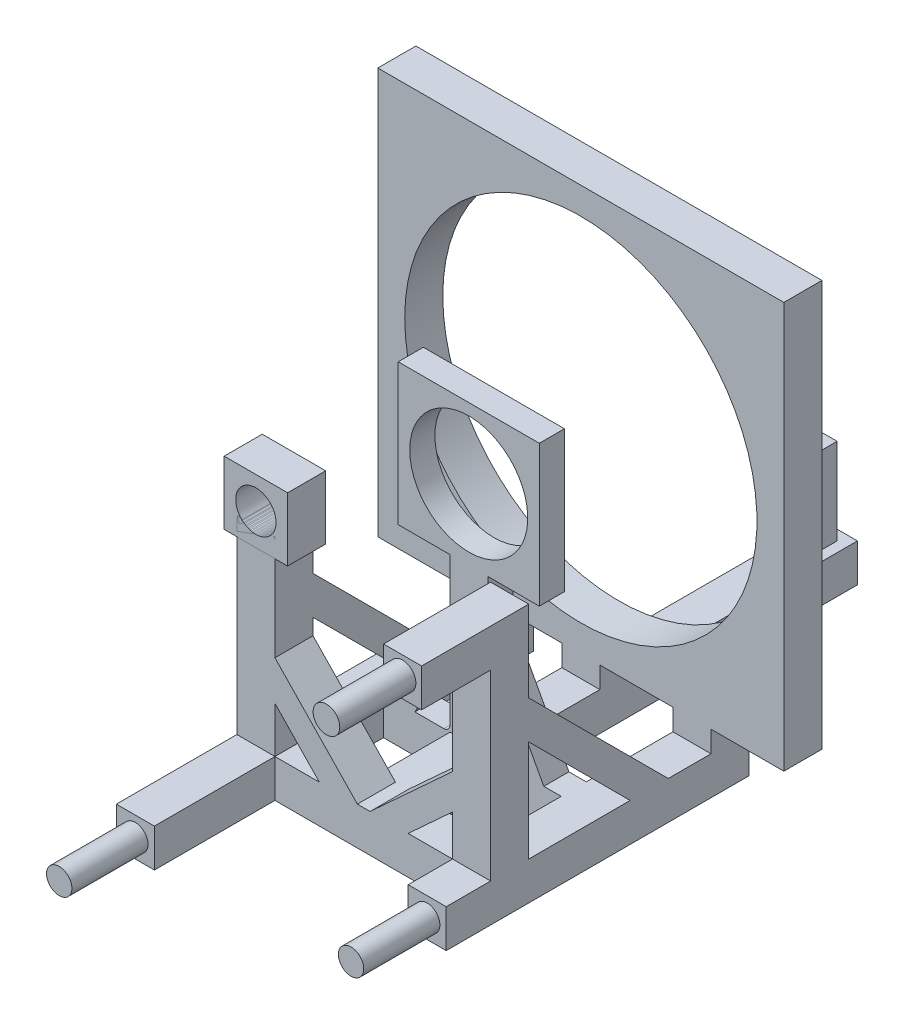
SolidWorks part; units mm, degrees
other "Markup1"
sketch "Sketch15" plane through (18.05, 14, 0) normal (0.0458, 0.1049, 0.9934) x (0.9989, -0.0157, -0.0444)
other "Markup2"
sketch "Sketch46" plane through (24.24, 35.18, 6) normal (0.2146, 0.4944, 0.8423) x (0.973, -0.1833, -0.1403)
ref_plane "Front Plane" through (0, 0, 0) normal (0, 0, 1) x (1, 0, 0)
ref_plane "Top Plane" through (0, 0, 0) normal (0, 1, 0) x (1, 0, 0)
ref_plane "Right Plane" through (0, 0, 0) normal (1, 0, 0) x (0, 0, -1)
sketch "Sketch3" plane through (0, 0, 0) normal (0, 0, 1) x (1, 0, 0)
  line L1 (-1.5, 1.5) -> (1.5, 1.5)
  line L2 (-1.5, 1.5) -> (-1.5, -1.5)
  line L3 (-1.5, -1.5) -> (1.5, -1.5)
  line L4 (1.5, 1.5) -> (1.5, -1.5)
  line L5 (-1.5, 1.5) -> (1.5, -1.5) construction
  line L6 (-1.5, -1.5) -> (1.5, 1.5) construction
  point P0 (0, 0)
  dimension "D1" = 3
  dimension "D3" = 0
  dimension "D2" = 3
  dimension "D4" = 0
sketch "Sketch4" plane through (0, 0, 0) normal (0, 1, 0) x (1, 0, 0)
  line L0 (0, 0) -> (0, 11)
  line L1 (0, 11) -> (17, 11)
  line L2 (17, 11) -> (17, 6)
  dimension "D1" = 17
  dimension "D2" = 11
  dimension "D3" = 5
sweep "Sweep3" add profiles "Sketch3" path "Sketch4"
sketch "Sketch7" plane through (0, 0, 0) normal (0, 1, 0) x (1, 0, 0)
  line L2 (-1.5, 12.5) -> (1.5, 12.5)
  line L3 (-1.5, 12.5) -> (-1.5, 9.5)
  line L4 (-1.5, 9.5) -> (1.5, 9.5)
  line L5 (1.5, 12.5) -> (1.5, 9.5)
  line L6 (-1.5, 12.5) -> (1.5, 9.5) construction
  line L7 (-1.5, 9.5) -> (1.5, 12.5) construction
  point P0 (0, 11)
  dimension "D1" = 1.5
  dimension "D2" = 3
extrude "Boss-Extrude1" add sketch "Sketch7" along normal blind 16.5
ref_plane "Plane8" through (0, 0, -11) normal (0, 0, 1) x (1, 0, 0)
sketch "Sketch12" plane through (0, 0, -11) normal (0, 0, 1) x (1, 0, 0)
  line L1 (-2.5, 20) -> (2.5, 20)
  line L2 (-2.5, 20) -> (-2.5, 15)
  line L3 (-2.5, 15) -> (2.5, 15)
  line L4 (2.5, 20) -> (2.5, 15)
  line L5 (-2.5, 20) -> (2.5, 15) construction
  line L6 (-2.5, 15) -> (2.5, 20) construction
  point P0 (0, 17.5)
  dimension "D1" = 17.5
  dimension "D2" = 5
  dimension "D3" = 1.5
  dimension "D4" = 5
extrude "Boss-Extrude4" add sketch "Sketch12" along normal mid plane 3 separate body
ref_plane "Plane9" through (9.09, 0, 0) normal (1, 0, 0) x (0, 0, -1)
sketch "Sketch16" plane through (0, 0, -12.5) normal (0, 0, -1) x (-1, 0, 0)
  circle A0 centre (0, 17.5) radius 1.59
sketch "Sketch17" plane through (0, 0, 0) normal (0, 0, 1) x (1, 0, 0)
  circle A0 centre (0, 0) radius 1
  dimension "D1" = 2
extrude "Boss-Extrude5" add sketch "Sketch17" along normal blind 6
sketch "Sketch18" plane through (0, 0, -6) normal (0, 0, 1) x (1, 0, 0)
  line L0 (18.5, 1.5) -> (18.5, -1.5) construction
  line L1 (15.5, 1.5) -> (18.5, 1.5) construction
  circle A0 centre (17, 0) radius 1
  dimension "D1" = 2
  dimension "D2" = 1.5
  dimension "D3" = 1.5
extrude "Boss-Extrude6" add sketch "Sketch18" along normal blind 6
ref_plane "Plane10" through (0, 0, -12.5) normal (0, 0, 1) x (1, 0, 0)
sketch "Sketch19" plane through (0, 0, -12.5) normal (0, 0, 1) x (1, 0, 0)
  line L0 (1.5, -1.5) -> (15.5, -1.5) construction
  line L1 (6.74, 1.5) -> (9.74, 1.5)
  line L2 (6.74, 1.5) -> (6.74, -1.5)
  line L3 (6.74, -1.5) -> (9.74, -1.5)
  line L4 (9.74, 1.5) -> (9.74, -1.5)
  line L5 (6.74, 1.5) -> (9.74, -1.5) construction
  line L6 (6.74, -1.5) -> (9.74, 1.5) construction
  point P0 (8.24, 0)
  dimension "D1" = 3
  dimension "D2" = 3
  dimension "D3" = 8.24
extrude "Boss-Extrude7" add sketch "Sketch19" against normal blind 7.54 separate body
sketch "Sketch21" plane through (0, 1.5, 0) normal (0, 1, 0) x (1, 0, 0)
  line L0 (9.74, 20.04) -> (9.74, 12.5) construction
  line L1 (6.74, 20.04) -> (9.74, 20.04)
  line L2 (6.74, 20.04) -> (6.74, 18.06)
  line L3 (6.74, 18.06) -> (9.74, 18.06)
  line L4 (9.74, 20.04) -> (9.74, 18.06)
  dimension "D2" = 1.98
extrude "Boss-Extrude8" add sketch "Sketch21" along normal blind 17.68
ref_plane "Plane11" through (0, 0, -19.05) normal (0, 0, 1) x (1, 0, 0)
sketch "Sketch22" plane through (0, 0, -19.05) normal (0, 0, 1) x (1, 0, 0)
  line L2 (2.6571, 24.74) -> (13.7771, 24.74)
  line L3 (2.6571, 24.74) -> (2.6571, 13.62)
  line L4 (2.6571, 13.62) -> (13.7771, 13.62)
  line L5 (13.7771, 24.74) -> (13.7771, 13.62)
  line L6 (2.6571, 24.74) -> (13.7771, 13.62) construction
  line L7 (2.6571, 13.62) -> (13.7771, 24.74) construction
  dimension "D3" = 11.12
  dimension "D4" = 11.12
extrude "Boss-Extrude9" add sketch "Sketch22" along normal mid plane 1.98
sketch "Sketch23" plane through (0, 0, -20.04) normal (0, 0, -1) x (-1, 0, 0)
  circle A0 centre (-8.2171, 19.18) radius 4.65
extrude "Cut-Extrude2" cut sketch "Sketch23" against normal mid plane 5
sketch "Sketch24" plane through (0, 0, -20.04) normal (0, 0, -1) x (-1, 0, 0)
  line L0 (-6.74, 1.5) -> (-9.74, 1.5) construction
  line L1 (-9.74, -1.5) -> (-6.74, -1.5)
  line L2 (-9.74, -1.5) -> (-9.74, 1.5)
  line L3 (-9.74, 1.5) -> (-6.74, 1.5)
  line L4 (-6.74, -1.5) -> (-6.74, 1.5)
  line L5 (-6.74, 1.5) -> (-9.74, 1.5) construction
extrude "Boss-Extrude10" add sketch "Sketch24" along normal blind 9.83
sketch "Sketch25" plane through (0, 1.5, 0) normal (0, 1, 0) x (1, 0, 0)
  line L0 (9.74, 29.87) -> (9.74, 20.04) construction
  line L1 (6.74, 29.87) -> (9.74, 29.87)
  line L2 (6.74, 29.87) -> (6.74, 26.87)
  line L3 (6.74, 26.87) -> (9.74, 26.87)
  line L4 (9.74, 29.87) -> (9.74, 26.87)
  dimension "D1" = 3
extrude "Boss-Extrude11" add sketch "Sketch25" along normal blind 3
ref_plane "Plane12" through (0, 0, -28.37) normal (0, 0, -1) x (-1, 0, 0)
sketch "Sketch27" plane through (0, 0, -28.37) normal (0, 0, -1) x (-1, 0, 0)
  line L2 (-24.24, 35.18) -> (7.76, 35.18)
  line L3 (-24.24, 35.18) -> (-24.24, 3.18)
  line L4 (-24.24, 3.18) -> (7.76, 3.18)
  line L5 (7.76, 35.18) -> (7.76, 3.18)
  line L6 (-24.24, 35.18) -> (7.76, 3.18) construction
  line L7 (-24.24, 3.18) -> (7.76, 35.18) construction
  line L8 (-6.74, 1.5) -> (-9.74, 1.5) construction
  point P0 (-8.24, 19.18)
  dimension "D1" = 17.68
  dimension "D3" = 32
extrude "Boss-Extrude12" add sketch "Sketch27" along normal mid plane 3
sketch "Sketch28" plane through (0, 0, -29.87) normal (0, 0, -1) x (-1, 0, 0)
  circle A0 centre (-8.24, 19.18) radius 13.88
extrude "Cut-Extrude3" cut sketch "Sketch28" against normal blind 7
sketch "Sketch31" plane through (0, 0, -29.87) normal (0, 0, -1) x (-1, 0, 0)
  line L0 (-6.74, 1.5) -> (-9.74, 1.5) construction
  line L1 (-9.74, -1.5) -> (-6.74, -1.5)
  line L2 (-9.74, -1.5) -> (-9.74, 1.5)
  line L3 (-9.74, 1.5) -> (-6.74, 1.5)
  line L4 (-6.74, -1.5) -> (-6.74, 1.5)
  line L5 (-6.74, 1.5) -> (-9.74, 1.5) construction
extrude "Boss-Extrude13" add sketch "Sketch31" along normal blind 17.3
sketch "Sketch32" plane through (0, 1.5, 0) normal (0, 1, 0) x (1, 0, 0)
  line L5 (6.74, 47.17) -> (6.74, 29.87) construction
  line L6 (7.54, 46.37) -> (8.94, 46.37)
  line L7 (7.54, 46.37) -> (7.54, 44.97)
  line L8 (7.54, 44.97) -> (8.94, 44.97)
  line L9 (8.94, 46.37) -> (8.94, 44.97)
  line L10 (7.54, 46.37) -> (8.94, 44.97) construction
  line L11 (7.54, 44.97) -> (8.94, 46.37) construction
  line L12 (6.74, 47.17) -> (9.74, 47.17) construction
  point P0 (8.24, 45.67)
  dimension "D1" = 1.4
  dimension "D2" = 1.4
  dimension "D3" = 1.5
  dimension "D4" = 1.5
extrude "Boss-Extrude14" add sketch "Sketch32" along normal blind 6.8
sketch "Sketch33" plane through (0, 0, -12.5) normal (0, 0, -1) x (-1, 0, 0)
  line L0 (1.5, -1.5) -> (-18.5, -1.5) construction
  line L1 (-18.5, 1.5) -> (-15.5, 1.5)
  line L2 (-18.5, 1.5) -> (-18.5, -1.5)
  line L3 (-18.5, -1.5) -> (-15.5, -1.5)
  line L4 (-15.5, 1.5) -> (-15.5, -1.5)
  dimension "D1" = 3
extrude "Boss-Extrude15" add sketch "Sketch33" along normal blind 17.37
sketch "Sketch34" plane through (0, 1.5, 0) normal (0, 1, 0) x (1, 0, 0)
  line L5 (15.5, 29.87) -> (18.5, 29.87) construction
  line L6 (15.5, 29.87) -> (18.5, 29.87)
  line L7 (15.5, 29.87) -> (15.5, 26.87)
  line L8 (15.5, 26.87) -> (18.5, 26.87)
  line L9 (18.5, 29.87) -> (18.5, 26.87)
  line L10 (18.5, 29.87) -> (18.5, 12.5) construction
  dimension "D1" = 3
  dimension "D2" = 3
extrude "Boss-Extrude16" add sketch "Sketch34" along normal blind 5.5
ref_plane "Plane13" through (8.5, 0, 0) normal (-1, 0, 0) x (0, 0, 1)
sketch "Sketch36" plane through (0, 1.5, 0) normal (0, 1, 0) x (1, 0, 0)
  line L0 (1.5, 12.5) -> (18.5, 12.5) construction
  line L1 (5, 12.5) -> (8, 12.5)
  line L2 (5, 12.5) -> (5, 9.5)
  line L3 (5, 9.5) -> (8, 9.5)
  line L4 (8, 12.5) -> (8, 9.5)
  line L5 (1.5, 9.5) -> (15.5, 9.5) construction
  line L6 (1.5, 9.5) -> (1.5, 12.5) construction
  point P10 (5, 11)
  dimension "D1" = 3
  dimension "D2" = 3.5
ref_plane "Plane14" through (0, 0, -11) normal (0, 0, 1) x (1, 0, 0)
sketch "Sketch39" plane through (0, 0, -11) normal (0, 0, 1) x (1, 0, 0)
  line L0 (6.5, 1.5) -> (0, 8.24)
  line L1 (0, 0) -> (0, 8.2619) construction
  line L7 (5, 1.5) -> (8, 1.5) construction
  dimension "D1" = 8.24
  dimension "D2" = 6.5
sweep "Sweep4" add profiles "Sketch36" path "Sketch39"
extrude "Cut-Extrude7" cut sketch "Sketch16" against normal mid plane 10
sketch "Sketch41" plane through (0, 0, -12.5) normal (0, 0, -1) x (-1, 0, 0)
  line L1 (1.5, -1.5) -> (-1.5, -1.5)
  line L2 (1.5, -1.5) -> (1.5, 1.5)
  line L3 (1.5, 1.5) -> (-1.5, 1.5)
  line L4 (-1.5, -1.5) -> (-1.5, 1.5)
  dimension "D1" = 3
extrude "Boss-Extrude17" add sketch "Sketch41" along normal blind 17.37
sketch "Sketch42" plane through (0, 1.5, 0) normal (0, 1, 0) x (1, 0, 0)
  line L0 (1.5, 29.87) -> (1.5, 12.5) construction
  line L1 (-1.5, 29.87) -> (1.5, 29.87)
  line L2 (-1.5, 29.87) -> (-1.5, 26.87)
  line L3 (-1.5, 26.87) -> (1.5, 26.87)
  line L4 (1.5, 29.87) -> (1.5, 26.87)
  dimension "D1" = 3
extrude "Boss-Extrude18" add sketch "Sketch42" along normal blind 5
sketch "Sketch43" plane through (0, 1.5, 0) normal (0, 1, 0) x (1, 0, 0)
  line L1 (15.5, 9.5) -> (18.5, 9.5)
  line L2 (15.5, 9.5) -> (15.5, 12.5)
  line L3 (15.5, 12.5) -> (18.5, 12.5)
  line L4 (18.5, 9.5) -> (18.5, 12.5)
extrude "Boss-Extrude19" add sketch "Sketch43" along normal blind 17.4
sketch "Sketch47" plane through (0, 1.5, 0) normal (0, 1, 0) x (1, 0, 0)
  line L0 (9.74, 12.5) -> (15.5, 12.5) construction
  line L1 (9, 12.5) -> (12, 12.5)
  line L2 (9, 12.5) -> (9, 9.5)
  line L3 (9, 9.5) -> (12, 9.5)
  line L4 (12, 12.5) -> (12, 9.5)
  line L5 (8, 9.5) -> (15.5, 9.5) construction
  line L6 (15.5, 12.5) -> (15.5, 9.5) construction
  dimension "D1" = 3
  dimension "D2" = 3.5
sketch "Sketch51" plane through (0, 0, -11) normal (0, 0, 1) x (1, 0, 0)
  line L0 (17, 0) -> (17, 9.292) construction
  line L1 (10.5, 1.5) -> (17, 7.472)
  line L3 (9, 1.5) -> (12, 1.5) construction
sweep "Sweep5" add profiles "Sketch47" path "Sketch51"
ref_plane "Plane15" through (0, 0, -12.5) normal (0, 0, 1) x (1, 0, 0)
sketch "Sketch53" plane through (0, 0, -12.5) normal (0, 0, 1) x (1, 0, 0)
  line L7 (-1.5, 16.5) -> (-1.5, 1.5) construction
  line L8 (-1.5, 12.5) -> (1.5, 12.5)
  line L9 (-1.5, 12.5) -> (-1.5, 9.5)
  line L10 (-1.5, 9.5) -> (1.5, 9.5)
  line L11 (1.5, 12.5) -> (1.5, 9.5)
  line L12 (1.5, 16.5) -> (1.5, 8.24) construction
  point P8 (-1.5, 11)
  dimension "D1" = 3
  dimension "D2" = 11
sketch "Sketch54" plane through (-1.5, 0, 0) normal (-1, 0, 0) x (0, 0, 1)
  line L0 (-12.5, 11) -> (-23.5, 0)
  line L1 (-12.5, 12.5) -> (-12.5, 9.5) construction
  line L2 (-12.5, -18.7014) -> (-12.5, 18.7014) construction
  dimension "D1" = 11
sweep "Sweep6" add profiles "Sketch53" path "Sketch54"
mirror "Mirror11" about plane through (8.5, 0, 0) normal (-1, 0, 0) of "Sweep6"
sketch "Sketch55" plane through (6.74, 0, 0) normal (-1, 0, 0) x (0, 0, 1)
  line L0 (-29.87, -1.5) -> (-12.5, -1.5) construction
  line L1 (-20.04, 1.5) -> (-18.06, 1.5)
  line L2 (-20.04, 1.5) -> (-20.04, -1.5)
  line L3 (-20.04, -1.5) -> (-18.06, -1.5)
  line L4 (-18.06, 1.5) -> (-18.06, -1.5)
extrude "Boss-Extrude20" add sketch "Sketch55" along normal up to next
sketch "Sketch56" plane through (9.74, 0, 0) normal (1, 0, 0) x (0, 0, -1)
  line L0 (20.04, 1.5) -> (18.06, 1.5) construction
  line L1 (18.06, 1.5) -> (20.04, 1.5)
  line L2 (18.06, 1.5) -> (18.06, -1.5)
  line L3 (18.06, -1.5) -> (20.04, -1.5)
  line L4 (20.04, 1.5) -> (20.04, -1.5)
  line L5 (20.5, 1.5) -> (12.5, 1.5) construction
extrude "Boss-Extrude21" add sketch "Sketch56" along normal up to next
fillet "Fillet1" radius 0.5 1 edges at (6.74, 1.5, -19.05)
fillet "Fillet2" radius 0.5 1 edges at (9.74, 1.5, -19.05)
sketch "Sketch57" plane through (6.74, 0, 0) normal (-1, 0, 0) x (0, 0, 1)
  line L0 (-20.04, 13.62) -> (-20.04, 2) construction
  line L1 (-20.04, 9.62) -> (-18.06, 9.62)
  line L2 (-20.04, 9.62) -> (-20.04, 6.62)
  line L3 (-20.04, 6.62) -> (-18.06, 6.62)
  line L4 (-18.06, 9.62) -> (-18.06, 6.62)
  line L5 (-18.06, 13.62) -> (-18.06, 2) construction
  line L6 (-18.06, 13.62) -> (-20.04, 13.62) construction
  dimension "D1" = 3
  dimension "D2" = 4
sketch "Sketch58" plane through (0, 0, -19.05) normal (0, 0, 1) x (1, 0, 0)
  line L0 (6.74, 8.12) -> (2.3492, 0)
  line L4 (6.74, 9.62) -> (6.74, 6.62) construction
sweep "Sweep7" add profiles "Sketch57" path "Sketch58"
ref_plane "Plane16" through (8.24, 0, 0) normal (-1, 0, 0) x (0, 0, 1)
mirror "Mirror13" about plane through (8.24, 0, 0) normal (-1, 0, 0) of "Sweep7"
sketch "Sketch59" plane through (0, 0, -9.5) normal (0, 0, 1) x (1, 0, 0)
  line L0 (18.5, 18.9) -> (18.5, 1.5) construction
  line L1 (15.5, 18.9) -> (18.5, 18.9)
  line L2 (15.5, 18.9) -> (15.5, 15.9)
  line L3 (15.5, 15.9) -> (18.5, 15.9)
  line L4 (18.5, 18.9) -> (18.5, 15.9)
  dimension "D1" = 3
extrude "Boss-Extrude22" add sketch "Sketch59" along normal blind 5.44
sketch "Sketch63" plane through (0, 0, -4.06) normal (0, 0, 1) x (1, 0, 0)
  line L4 (15.5, 18.9) -> (15.5, 15.9)
  line L5 (15.5, 15.9) -> (18.5, 15.9)
  line L6 (18.5, 15.9) -> (18.5, 18.9)
  line L7 (18.5, 18.9) -> (15.5, 18.9)
  line L8 (15.5, 18.9) -> (15.5, 15.9)
  line L9 (15.5, 15.9) -> (18.5, 15.9)
  line L10 (18.5, 15.9) -> (18.5, 18.9)
  line L11 (18.5, 18.9) -> (15.5, 18.9)
  circle A0 centre (17, 17.5) radius 1.05 construction
  circle A1 centre (17, 17.5) radius 1.05
  dimension "D1" = 0
extrude "Boss-Extrude25" add sketch "Sketch63" along normal blind 6 contours A1
